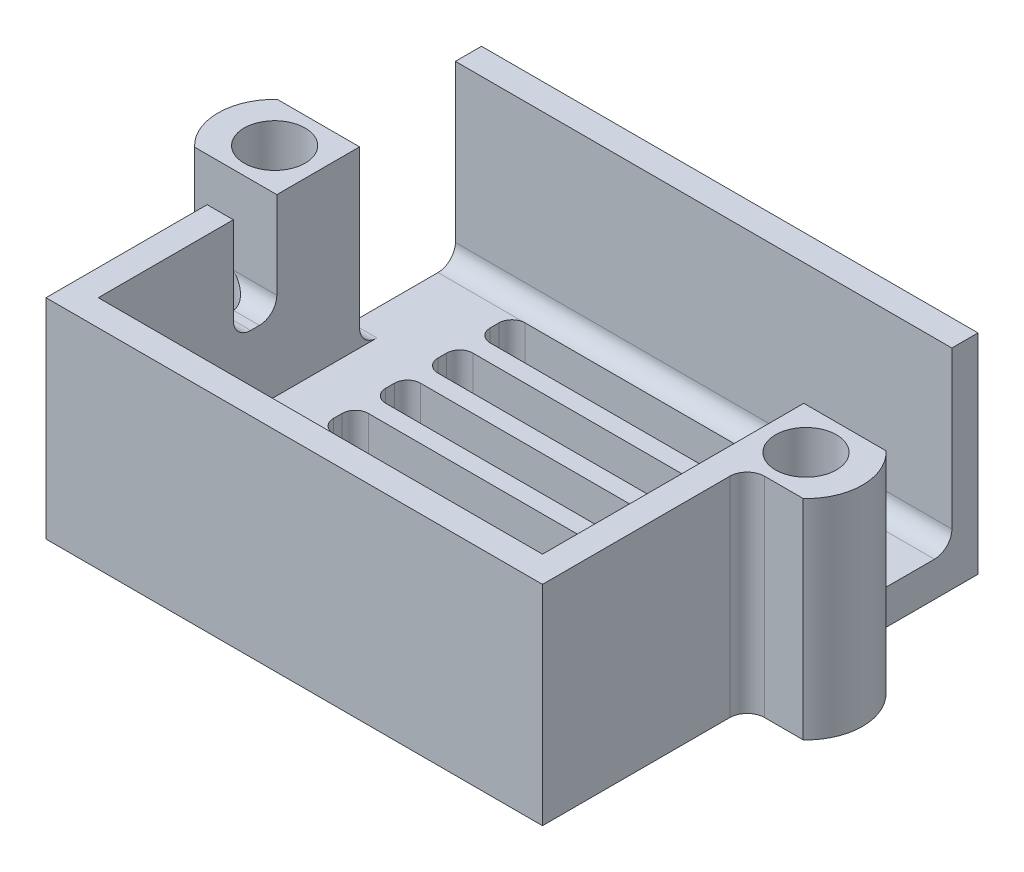
SolidWorks part; units mm, degrees
ref_plane "Front Plane" through (0, 0, 0) normal (0, 0, 1) x (1, 0, 0)
ref_plane "Top Plane" through (0, 0, 0) normal (0, 1, 0) x (1, 0, 0)
ref_plane "Right Plane" through (0, 0, 0) normal (1, 0, 0) x (0, 0, -1)
sketch "Sketch1" plane through (0, 0, 0) normal (0, 1, 0) x (1, 0, 0)
  line L0 (0, 11) -> (0, -11) construction
  line L1 (-12.75, 11) -> (12.75, 11)
  line L2 (-12.75, 11) -> (-12.75, -11)
  line L3 (-12.75, -11) -> (12.75, -11)
  line L4 (12.75, 11) -> (12.75, -11)
  line L5 (-12.75, 11) -> (12.75, -11) construction
  line L6 (-12.75, -11) -> (12.75, 11) construction
  line L7 (14.25, 12.5) -> (-14.25, 12.5)
  line L8 (14.25, 12.5) -> (14.25, -12.5)
  line L9 (14.25, -12.5) -> (-14.25, -12.5)
  line L10 (-14.25, 12.5) -> (-14.25, -12.5)
  line L11 (14.25, 12.5) -> (-14.25, -12.5) construction
  line L12 (14.25, -12.5) -> (-14.25, 12.5) construction
  line L13 (-9.25, 5) -> (9.25, 5)
  line L14 (-9.25, 4) -> (9.25, 4)
  line L15 (-10, 3.25) -> (-10, 2.75)
  line L16 (-9.25, 2) -> (9.25, 2)
  line L17 (10, 3.25) -> (10, 2.75)
  line L18 (-10, 4) -> (10, 2) construction
  line L19 (-10, 2) -> (10, 4) construction
  line L20 (-10, 6.25) -> (-10, 5.75)
  line L21 (-9.25, 7) -> (9.25, 7)
  line L22 (10, 6.25) -> (10, 5.75)
  line L23 (-9.25, 8) -> (9.25, 8)
  line L24 (-10, 9.25) -> (-10, 8.75)
  line L25 (-9.25, 10) -> (9.25, 10)
  line L26 (10, 9.25) -> (10, 8.75)
  line L27 (-12.75, 0) -> (12.75, 0) construction
  line L28 (-10, -2) -> (10, -4) construction
  line L29 (-10, -4) -> (10, -2) construction
  line L30 (10, -9.25) -> (10, -8.75)
  line L31 (-9.25, -10) -> (9.25, -10)
  line L32 (-10, -9.25) -> (-10, -8.75)
  line L33 (-9.25, -8) -> (9.25, -8)
  line L34 (10, -6.25) -> (10, -5.75)
  line L35 (-9.25, -7) -> (9.25, -7)
  line L36 (-10, -6.25) -> (-10, -5.75)
  line L37 (10, -3.25) -> (10, -2.75)
  line L38 (-9.25, -2) -> (9.25, -2)
  line L39 (-10, -3.25) -> (-10, -2.75)
  line L40 (-9.25, -4) -> (9.25, -4)
  line L41 (-9.25, -5) -> (9.25, -5)
  line L42 (-10, 0.25) -> (-10, -0.25)
  line L43 (10, 0.25) -> (10, -0.25)
  line L44 (-9.25, 1) -> (9.25, 1)
  line L45 (-9.25, -1) -> (9.25, -1)
  arc A0 (9.25, 4) -> (10, 3.25) centre (9.25, 3.25) cw
  arc A1 (-10, 2.75) -> (-9.25, 2) centre (-9.25, 2.75) ccw
  arc A2 (9.25, 2) -> (10, 2.75) centre (9.25, 2.75) ccw
  arc A3 (-9.25, 4) -> (-10, 3.25) centre (-9.25, 3.25) ccw
  arc A4 (-10, 5.75) -> (-9.25, 5) centre (-9.25, 5.75) ccw
  arc A5 (-9.25, 7) -> (-10, 6.25) centre (-9.25, 6.25) ccw
  arc A6 (9.25, 5) -> (10, 5.75) centre (9.25, 5.75) ccw
  arc A7 (9.25, 7) -> (10, 6.25) centre (9.25, 6.25) cw
  arc A8 (-10, 8.75) -> (-9.25, 8) centre (-9.25, 8.75) ccw
  arc A9 (-9.25, 10) -> (-10, 9.25) centre (-9.25, 9.25) ccw
  arc A10 (9.25, 8) -> (10, 8.75) centre (9.25, 8.75) ccw
  arc A11 (9.25, 10) -> (10, 9.25) centre (9.25, 9.25) cw
  arc A12 (9.25, -10) -> (10, -9.25) centre (9.25, -9.25) ccw
  arc A13 (9.25, -8) -> (10, -8.75) centre (9.25, -8.75) cw
  arc A14 (-9.25, -10) -> (-10, -9.25) centre (-9.25, -9.25) cw
  arc A15 (-10, -8.75) -> (-9.25, -8) centre (-9.25, -8.75) cw
  arc A16 (9.25, -7) -> (10, -6.25) centre (9.25, -6.25) ccw
  arc A17 (9.25, -5) -> (10, -5.75) centre (9.25, -5.75) cw
  arc A18 (-9.25, -7) -> (-10, -6.25) centre (-9.25, -6.25) cw
  arc A19 (-10, -5.75) -> (-9.25, -5) centre (-9.25, -5.75) cw
  arc A20 (-9.25, -4) -> (-10, -3.25) centre (-9.25, -3.25) cw
  arc A21 (9.25, -2) -> (10, -2.75) centre (9.25, -2.75) cw
  arc A22 (-10, -2.75) -> (-9.25, -2) centre (-9.25, -2.75) cw
  arc A23 (9.25, -4) -> (10, -3.25) centre (9.25, -3.25) ccw
  arc A24 (9.25, 1) -> (10, 0.25) centre (9.25, 0.25) cw
  arc A25 (-9.25, 1) -> (-10, 0.25) centre (-9.25, 0.25) ccw
  arc A26 (-10, -0.25) -> (-9.25, -1) centre (-9.25, -0.25) ccw
  arc A27 (9.25, -1) -> (10, -0.25) centre (9.25, -0.25) ccw
  point P0 (0, 0)
  point P6 (0, 0)
  point P13 (0, 3)
  point P96 (0, -3)
  dimension "D8" = 0.75
  dimension "D1" = 25.5
  dimension "D2" = 22
  dimension "D3" = 1.5
  dimension "D4" = 1.5
  dimension "D5" = 20
  dimension "D6" = 2
  dimension "D7" = 3
  dimension "D10" = 3
  dimension "D12" = 3
  dimension "D9" = 3
  dimension "D11" = 2
extrude "Boss-Extrude1" add sketch "Sketch1" along normal blind 2 contours L7 L10 L9 L8 L1 L4 L3 L2 | L4 L1 L2 L3 A27 L45 A26 L42 A25 L44 A24 L43 A23 L40 A20 L39 A22 L38 A21 L37 L32 A15 L33 A13 L30 A12 L31 A14 L21 A7 L22 A6 L13 A4 L20 A5 A3 L14 A0 L17 A2 L16 A1 L15 L25 region at (0, 0, -10.6632) region at (13.8709, 0, 0)
sketch "Sketch2" plane through (0, 2, 0) normal (0, 1, 0) x (1, 0, 0)
  line L1 (12.75, 11) -> (-12.75, 11)
  line L2 (12.75, 11) -> (12.75, -11)
  line L3 (12.75, -11) -> (-12.75, -11)
  line L4 (14.25, 12.5) -> (-14.25, 12.5)
  line L5 (-14.25, 12.5) -> (-14.25, -12.5)
  line L6 (-14.25, -12.5) -> (14.25, -12.5)
  line L7 (14.25, -12.5) -> (14.25, 12.5)
  line L8 (14.25, 12.5) -> (-14.25, 12.5)
  line L9 (-14.25, 12.5) -> (-14.25, -12.5)
  line L10 (-14.25, -12.5) -> (14.25, -12.5)
  line L11 (14.25, -12.5) -> (14.25, 12.5)
  line L12 (-12.75, 11) -> (-12.75, -11)
  line L13 (12.75, 11) -> (-12.75, -11) construction
  line L14 (12.75, -11) -> (-12.75, 11) construction
  point P2 (0, 0)
  dimension "D2" = 1.5
  dimension "D3" = 1.5
  dimension "D1" = 0
extrude "Boss-Extrude2" add sketch "Sketch2" along normal blind 10
sketch "Sketch3" plane through (0, 12, 0) normal (0, 1, 0) x (1, 0, 0)
  line L0 (-14.25, 12.5) -> (-14.25, -12.5) construction
  line L1 (-12.75, 11) -> (-14.25, 11)
  line L2 (-12.75, 11) -> (-12.75, 4)
  line L3 (-12.75, 4) -> (-14.25, 4)
  line L4 (-14.25, 11) -> (-14.25, 4)
  line L5 (14.25, -12.5) -> (14.25, 12.5) construction
  line L6 (12.75, 11) -> (14.25, 11)
  line L7 (12.75, 11) -> (12.75, 4)
  line L8 (12.75, 4) -> (14.25, 4)
  line L9 (14.25, 11) -> (14.25, 4)
  dimension "D1" = 7
extrude "Cut-Extrude1" cut sketch "Sketch3" against normal up to surface (10 mm away) up to face at (0, 2, 0)
sketch "Sketch4" plane through (0, 12, 0) normal (0, 1, 0) x (1, 0, 0)
  line L0 (-14.25, 4) -> (-14.25, -12.5) construction
  line L1 (-14.25, -0.75) -> (-12.75, -0.75)
  line L2 (-14.25, -0.75) -> (-14.25, -3.25)
  line L3 (-14.25, -3.25) -> (-12.75, -3.25)
  line L4 (-12.75, -0.75) -> (-12.75, -3.25)
  line L5 (-12.75, 4) -> (-12.75, -11) construction
  line L6 (-14.25, -2) -> (-12.75, -2) construction
  line L8 (14.25, 11) -> (-14.25, 11) construction
  dimension "D1" = 2.5
  dimension "D2" = 13
extrude "Cut-Extrude2" cut sketch "Sketch4" against normal blind 6
sketch "Sketch5" plane through (0, 0, 0) normal (0, -1, 0) x (1, 0, 0)
  line L0 (-15.25, -3.375) -> (-15.25, 0.125) construction
  line L3 (-14.25, -1.625) -> (-26.0678, -1.625) construction
  line L7 (-14.25, -1.625) -> (-12.75, -1.625) construction
  line L8 (-14.25, -4) -> (-14.25, 0.75) construction
  line L9 (-12.75, -4) -> (-12.75, 0.75) construction
  line L12 (-13.5, -4) -> (-13.5, 0.75) construction
  line L13 (-12.75, -4) -> (-14.25, -4) construction
  line L14 (-12.75, 0.75) -> (-14.25, 0.75) construction
  line L15 (-14.25, -4) -> (-17.4685, -4)
  line L16 (-14.25, 0.75) -> (-17.4685, 0.75)
  line L17 (-14.25, 0.75) -> (-14.25, -4)
  line L18 (14.25, -4) -> (17.4685, -4)
  line L19 (14.25, 0.75) -> (17.4685, 0.75)
  line L20 (0, 12.5) -> (0, -12.5) construction
  line L21 (-14.25, 12.5) -> (14.25, 12.5) construction
  line L22 (14.25, -12.5) -> (-14.25, -12.5) construction
  line L23 (14.25, 0.75) -> (14.25, -4)
  circle A0 centre (-15.25, -1.625) radius 1.75
  circle A1 centre (-15.25, -1.625) radius 3.25
  circle A2 centre (15.25, -1.625) radius 3.25
  dimension "D1" = 3.5
  dimension "D2" = 1.5
extrude "Boss-Extrude3" add sketch "Sketch5" against normal up to surface (12 mm away) contours L17 A0 | L16 A1 L15 L17 A0 | A2 L19 L23 L18 region at (-15.8593, 0, -3.9363) region at (-15.4935, 0, -1.625) region at (16.227, 0, -1.625) up to face at (-13.5, 12, -1.625)
sketch "Sketch6" plane through (0, 0, 0) normal (0, -1, 0) x (1, 0, 0)
  line L0 (0, 12.5) -> (0, -12.5) construction
  line L1 (14.25, 12.5) -> (-14.25, 12.5) construction
  line L2 (14.25, -12.5) -> (-14.25, -12.5) construction
  circle A0 centre (-15.25, -1.625) radius 1.75
  circle A1 centre (15.25, -1.625) radius 1.75
  dimension "D1" = 3.5
extrude "Cut-Extrude3" cut sketch "Sketch6" against normal up to next
fillet "Fillet1" radius 1 9 edges at (-13.5, 6, 3.25) (0, 2, -11)
equation "\"wallWidth\"=1.5"
equation "\"D3@Sketch1\"=\"wallWidth\""
equation "\"D4@Sketch1\"=\"wallWidth\""
equation "\"D2@Sketch2\"=\"wallWidth\""
equation "\"D3@Sketch2\"=\"wallWidth\""
equation "\"ˇ3.5\"=1.92814"
equation "\"D2@Sketch5\"=\"wallWidth\""
